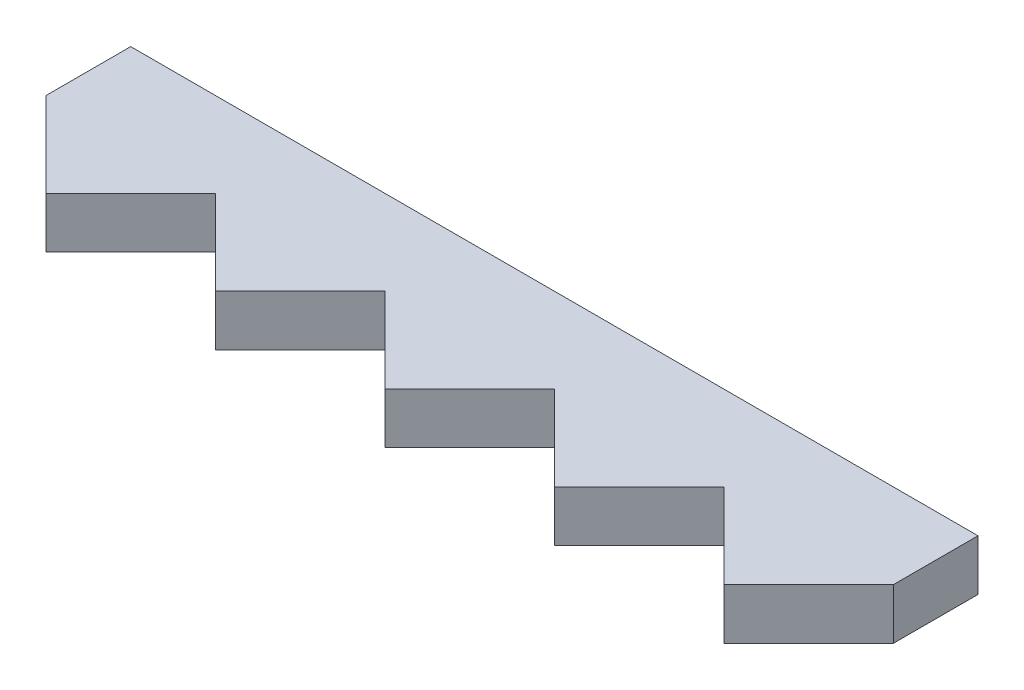
SolidWorks part; units mm, degrees
material "Custom Plastic"
ref_plane "Front Plane" through (0, 0, 0) normal (0, 0, 1) x (1, 0, 0)
ref_plane "Top Plane" through (0, 0, 0) normal (0, 1, 0) x (1, 0, 0)
ref_plane "Right Plane" through (0, 0, 0) normal (1, 0, 0) x (0, 0, -1)
sketch "Sketch1" plane through (0, 3, 0) normal (0, 1, 0) x (1, 0, 0)
  line L0 (0, 71.6064) -> (0, 66.6064)
  line L2 (0, 66.6064) -> (5, 61.6064)
  line L3 (5, 61.6064) -> (10, 66.6064)
  line L7 (10, 66.6064) -> (15, 61.6064)
  line L8 (15, 61.6064) -> (20, 66.6064)
  line L9 (20, 66.6064) -> (25, 61.6064)
  line L10 (25, 61.6064) -> (30, 66.6064)
  line L11 (30, 66.6064) -> (35, 61.6064)
  line L12 (35, 61.6064) -> (40, 66.6064)
  line L13 (40, 66.6064) -> (45, 61.6064)
  line L14 (45, 61.6064) -> (50, 66.6064)
  line L19 (0, 71.6064) -> (50, 71.6064)
  line L20 (50, 71.6064) -> (50, 66.6064)
  dimension "D1" = 5
  dimension "D2" = 5
  dimension "D3" = 10
  dimension "D4" = 5
extrude "Boss-Extrude1" add sketch "Sketch1" along normal blind 3
